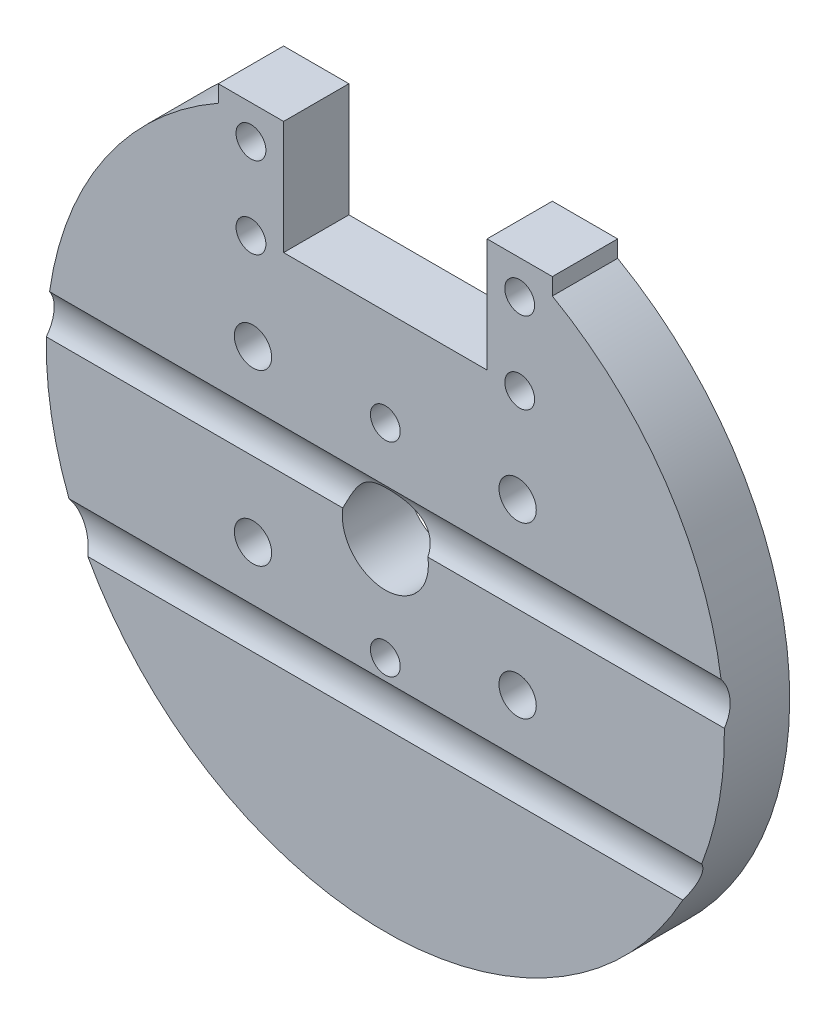
SolidWorks part; units mm, degrees
material "6061 Alloy"
ref_plane "Front Plane" through (0, 0, 0) normal (0, 0, 1) x (1, 0, 0)
ref_plane "Top Plane" through (0, 0, 0) normal (0, 1, 0) x (1, 0, 0)
ref_plane "Right Plane" through (0, 0, 0) normal (1, 0, 0) x (0, 0, -1)
sketch "Sketch1" plane through (0, 0, 0) normal (0, 0, 1) x (1, 0, 0)
  circle A0 centre (0, 0) radius 50
  dimension "D1" = 100
extrude "3/8" add sketch "Sketch1" along normal blind 9.63
sketch "Sketch2" plane through (0, 0, 9.63) normal (0, 0, 1) x (1, 0, 0)
  line L0 (0, 0) -> (0, 50) construction
  line L1 (-1.318, 74.311) -> (-1.318, 76.1424) construction
  line L3 (-15, 46) -> (-15, 29.25)
  line L4 (-15, 29.25) -> (15, 29.25)
  line L5 (15, 46) -> (15, 29.25)
  line L6 (0, 0) -> (0, 50) construction
  line L7 (-15, 37.625) -> (15, 37.625) construction
  line L8 (-30.7361, 76.1424) -> (28.1002, 76.1424)
  line L9 (-30.7361, 76.1424) -> (-30.7361, 46)
  line L10 (-30.7361, 46) -> (-15, 46)
  line L11 (28.1002, 76.1424) -> (28.1002, 46)
  line L12 (15, 46) -> (28.1002, 46)
  line L13 (-30.7361, 61.0712) -> (28.1002, 61.0712) construction
  circle A0 centre (0, 0) radius 50 construction
  point P6 (0, 37.625)
  point P130 (-1.318, 61.0712)
  dimension "D1" = 30
  dimension "D2" = 29.25
  dimension "D3" = 46
extrude "Cut-Extrude1" cut sketch "Sketch2" against normal up to surface (9.63 mm away) up to face at (50, 0, 0)
sketch "Sketch3" plane through (0, 0, 9.63) normal (0, 0, 1) x (1, 0, 0)
  line L1 (-15, 29.25) -> (-24.63, 29.25)
  line L2 (-15, 29.25) -> (-15, 46)
  line L3 (-15, 46) -> (-24.63, 46)
  line L4 (-24.63, 29.25) -> (-24.63, 46)
  line L5 (-19.815, 46) -> (-19.815, 29.25) construction
  line L6 (-15, 37.625) -> (-24.63, 37.625) construction
  line L7 (15, 29.25) -> (24.63, 29.25)
  line L8 (15, 29.25) -> (15, 46)
  line L9 (15, 46) -> (24.63, 46)
  line L10 (24.63, 29.25) -> (24.63, 46)
  line L11 (19.815, 46) -> (19.815, 29.25) construction
  line L12 (15, 37.625) -> (24.63, 37.625) construction
  point P168 (19.815, 37.625)
  point P204 (-19.815, 37.625)
  dimension "D1" = 9.63
  dimension "D2" = 9.63
  dimension "D3" = 46
extrude "Boss-Extrude2" add sketch "Sketch3" against normal up to surface (9.63 mm away) up to face at (0, 24.4167, 0)
sketch "Sketch4" plane through (0, 0, 9.63) normal (0, 0, 1) x (1, 0, 0)
  line L0 (-15, 35) -> (-24.63, 35) construction
  line L2 (-24.63, 46) -> (-24.63, 43.5128) construction
  line L3 (-19.815, 41) -> (-19.815, 35) construction
  line L4 (0, 0) -> (0, 50.3734) construction
  line L5 (-15, 46) -> (-15, 29.25) construction
  circle A0 centre (-19.815, 41) radius 2.2
  circle A1 centre (-19.815, 29) radius 2.2
  circle A2 centre (19.815, 29) radius 2.2
  circle A3 centre (19.815, 41) radius 2.2
  point P2 (0, 0)
  dimension "D1" = 4.4
  dimension "D2" = 6
  dimension "D3" = 35
extrude "M4_through" cut sketch "Sketch4" against normal up to surface (9.63 mm away) up to face at (0, 29.5016, 0)
sketch "Sketch5" plane through (0, 0, 9.63) normal (0, 0, 1) x (1, 0, 0)
  circle A0 centre (0, 0) radius 6.35
  dimension "D1" = 12.7
extrude "Cut-Extrude2" cut sketch "Sketch5" against normal up to surface (9.63 mm away) up to face at (22.015, 41, 0)
sketch "Sketch6" plane through (0, 0, 9.63) normal (0, 0, 1) x (1, 0, 0)
  circle A0 centre (0, 0) radius 15 construction
  circle A1 centre (0, 15) radius 2.2
  circle A2 centre (0, -15) radius 2.2
  point P13 (0, 0)
  dimension "D1" = 30
  dimension "D2" = 4.4
  dimension "D3" = 2
extrude "M4_through2" cut sketch "Sketch6" against normal up to surface (9.63 mm away) up to face at (6.35, 0, 0)
sketch "Sketch7" plane through (0, 0, 9.63) normal (0, 0, 1) x (1, 0, 0)
  line L0 (0, 0) -> (0, 38.8961) construction
  line L1 (-19.51, 15) -> (-19.51, -10) construction
  circle A0 centre (-19.51, 15) radius 2.75
  circle A1 centre (-19.51, -10) radius 2.75
  circle A2 centre (19.51, -10) radius 2.75
  circle A3 centre (19.51, 15) radius 2.75
  circle A4 centre (0, 0) radius 30 construction
  dimension "D2" = 5.5
  dimension "D3" = 25
  dimension "D4" = 60
  dimension "D1" = 19.51
  dimension "D5" = 15
extrude "M5_through" cut sketch "Sketch7" against normal up to surface (9.63 mm away) up to face at (2.2, 15, 0)
chamfer "Chamfer1" distance 2.5 angle 45 4 edges at (22.015, 41, 0) (-17.615, 29, 0) (-17.615, 41, 0) (22.015, 29, 0)
sketch "Sketch8" plane through (0, 0, 0) normal (1, 0, 0) x (0, 0, -1)
  line L0 (-13.63, 4) -> (-9.63, 4) construction
  line L2 (-9.63, 43.5128) -> (-9.63, -50) construction
  line L4 (-13.63, -21) -> (-9.63, -21) construction
  line L6 (-13.63, 4) -> (-13.63, -21) construction
  line L7 (-9.63, 17.75) -> (-9.63, 12.25) construction
  circle A0 centre (-13.63, 4) radius 5
  circle A1 centre (-13.63, -21) radius 5
  point P4 (-9.63, 15)
  dimension "D1" = 10
  dimension "D2" = 4
  dimension "D3" = 11
  dimension "D4" = 25
extrude "Cut-Extrude4" cut sketch "Sketch8" against normal through all and the other way through all
